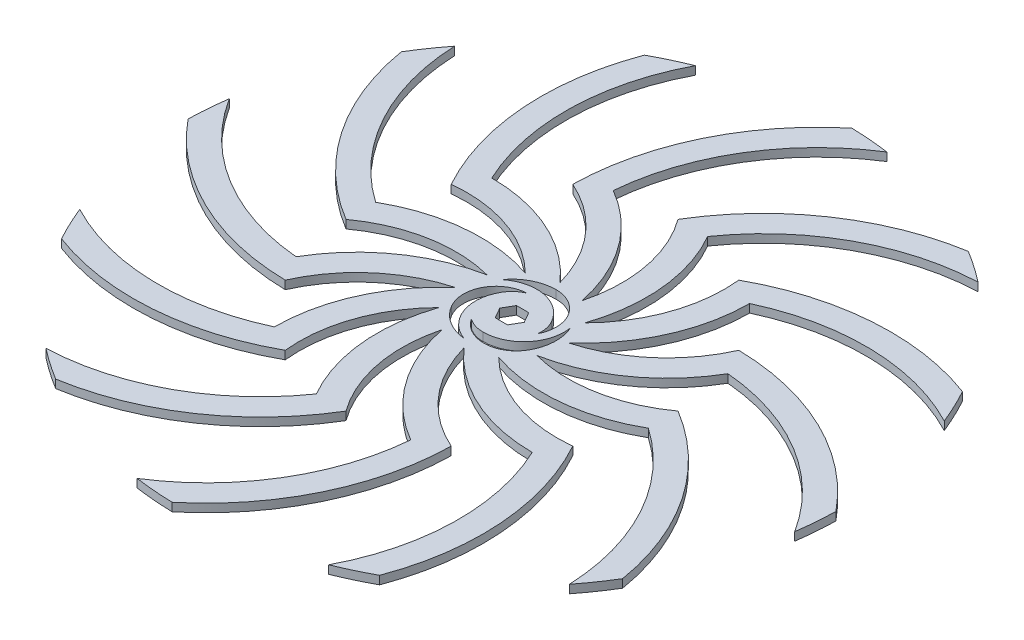
SolidWorks part; units mm, degrees
ref_plane "Front Plane" through (0, 0, 0) normal (0, 0, 1) x (1, 0, 0)
ref_plane "Top Plane" through (0, 0, 0) normal (0, 1, 0) x (1, 0, 0)
ref_plane "Right Plane" through (0, 0, 0) normal (1, 0, 0) x (0, 0, -1)
sketch "Sketch1" plane through (0, 0, 0) normal (0, 1, 0) x (1, 0, 0)
  line L0 (0, 0) -> (3.5728, 0)
  line L1 (0, 0) -> (0, 40) construction
  circle A0 centre (0, 0) radius 40
  circle A1 centre (0, 0) radius 42
  arc A2 (0, 0) -> (0, 20) centre (-13.7477, 10) ccw
  arc A3 (3.5728, 0) -> (3.5728, 20) centre (-13.7477, 10) ccw
  arc A4 (0, 20) -> (20.8254, 34.1512) centre (25.7173, 4.5527) cw
  arc A5 (3.5728, 20) -> (24.614, 31.5301) centre (25.7173, 4.5527) cw
  point P13 (0, 20)
  dimension "D1" = 80
  dimension "D2" = 84
  dimension "D3" = 17
  dimension "D4" = 20
  dimension "D5" = 30
  dimension "D6" = 27
extrude "Boss-Extrude1" add sketch "Sketch1" along normal blind 1 contours A3 A5 A0 A4 A2 L0 region at (3.6732, 0, -10)
ref_axis "Axis1" through (0, 0, 0) along (0, 1, 0)
pattern_circular "CirPattern1" count 12 over 360 about axis through (0, 0, 0) along (0, 1, 0) of bodies 101
sketch "Sketch2" plane through (0, 0, 0) normal (0, 1, 0) x (1, 0, 0)
  arc A0 (0, 0) -> (20, 0) centre (10, 13.7477) ccw construction
  arc A1 (1.7864, -3.0941) -> (19.1069, 6.9059) centre (1.7864, 16.9059) ccw construction
  arc A2 (0, 0) -> (20, 0) centre (10, 13.7477) ccw
  arc A3 (1.7864, -3.0941) -> (19.1069, 6.9059) centre (1.7864, 16.9059) ccw
  circle A4 centre (0, 0) radius 6.3246
  point P7 (5.7174, -2.704)
extrude "Boss-Extrude2" add sketch "Sketch2" along normal up to surface (1 mm away) contours A4 region at (5.9964, 0, 1.3465) up to face at (-20.5854, 1, 1.1757)
sketch "Sketch3" plane through (0, 1, 0) normal (0, 1, 0) x (1, 0, 0)
  line L0 (0, 0) -> (0, 1.4123) construction
  arc A0 (-2.1651, 1.25) -> (4.6112, -2.6623) centre (1.2231, -0.7061) ccw
  circle A1 centre (0, 0) radius 6.3246
  circle A2 centre (0, 0) radius 6.3246
  arc A3 (-3.0311, 1.75) -> (-0.5188, -5.2992) centre (1.2231, -0.7061) ccw
  circle A4 centre (0, 0) radius 5.3246
  circle A5 centre (0, 0) radius 2.5
  arc A6 (0, -2.5) -> (0, 5.3246) centre (0, 1.4123) ccw
  circle A7 centre (0, 0) radius 3.5
  arc A8 (0, -3.5) -> (4.8487, 2.2003) centre (0, 1.4123) ccw
  arc A9 (2.1651, 1.25) -> (-4.6112, -2.6623) centre (-1.2231, -0.7061) ccw
  arc A10 (3.0311, 1.75) -> (-4.3299, 3.0989) centre (-1.2231, -0.7061) ccw
  dimension "D3" = 5
  dimension "D4" = 7
  dimension "D1" = 0
  dimension "D2" = 1
  dimension "D5" = 3
extrude "Cut-Extrude1" cut sketch "Sketch3" against normal through all contours A7 A9 A4 A3 | A10 A7 A6 A4 | A8 A7 A0 A4 region at (2.7046, 1, 2.7563) region at (-3.7394, 1, 0.9641) region at (1.0347, 1, -3.7204)
scale "Scale1" scale about centroid uniform scaling yes scale factor 3.4
sketch "Sketch4" plane through (0, 2.2, 0) normal (0, 1, 0) x (1, 0, 0)
  line L1 (0, 7.3323) -> (-6.35, 3.6662) construction
  line L2 (-6.35, 3.6662) -> (-6.35, -3.6662) construction
  line L3 (-6.35, -3.6662) -> (0, -7.3323) construction
  line L4 (0, -7.3323) -> (6.35, -3.6662) construction
  line L5 (6.35, -3.6662) -> (6.35, 3.6662) construction
  line L6 (6.35, 3.6662) -> (0, 7.3323) construction
  line L7 (2.5115, -4.35) -> (5.0229, 0)
  line L8 (5.0229, 0) -> (2.5115, 4.35)
  line L9 (2.5115, 4.35) -> (-2.5115, 4.35)
  line L10 (-2.5115, 4.35) -> (-5.0229, 0)
  line L11 (-5.0229, 0) -> (-2.5115, -4.35)
  line L12 (-2.5115, -4.35) -> (2.5115, -4.35)
  circle A0 centre (0, 0) radius 6.35 construction
  circle A1 centre (0, 0) radius 5.0229
  circle A2 centre (0, 0) radius 4.35 construction
  dimension "D1" = 12.7
  dimension "D2" = 8.7
extrude "Cut-Extrude2" cut sketch "Sketch4" against normal up to surface (3.4 mm away) contours L11 L12 L7 L8 L9 L10 region at (0, 2.2, 0) up to face at (7.8986, -1.2, 8.4784)
